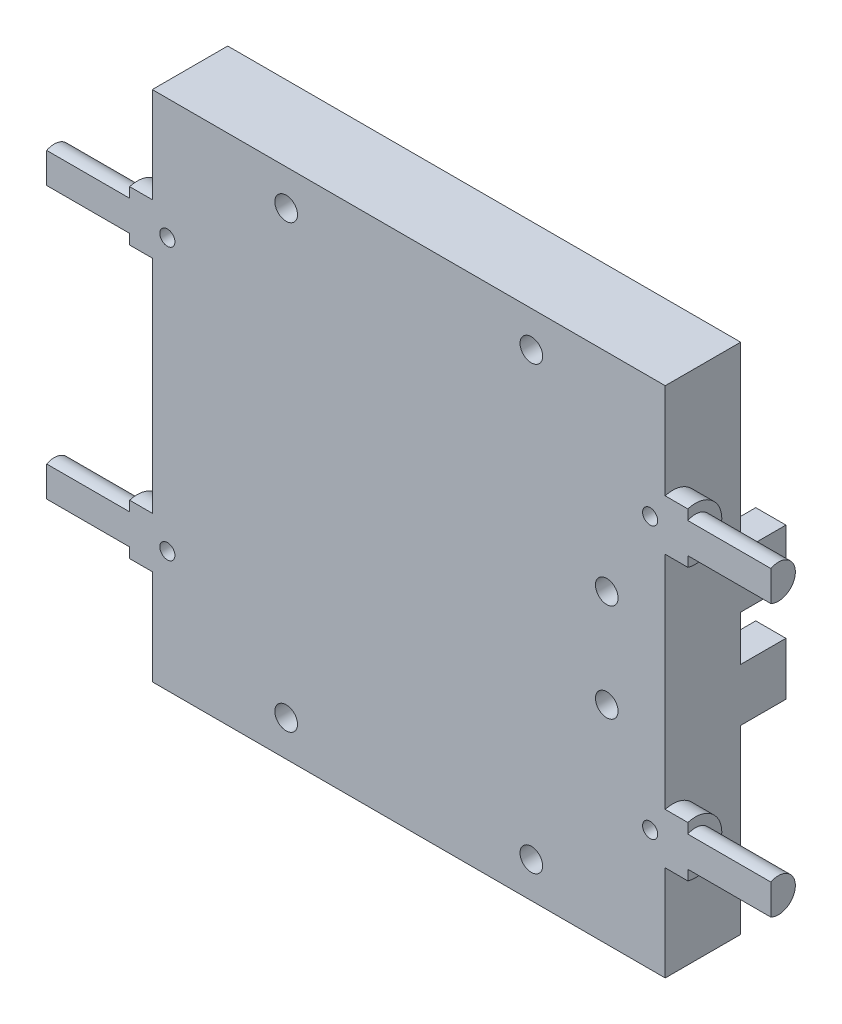
SolidWorks part; units mm, degrees
ref_plane "Front Plane" through (0, 0, 0) normal (0, 0, 1) x (1, 0, 0)
ref_plane "Top Plane" through (0, 0, 0) normal (0, 1, 0) x (1, 0, 0)
ref_plane "Right Plane" through (0, 0, 0) normal (1, 0, 0) x (0, 0, -1)
sketch "Sketch1" plane through (0, 0, 0) normal (0, 0, 1) x (1, 0, 0)
  line L1 (0, 0) -> (-68, 0)
  line L2 (0, 0) -> (0, -68)
  line L3 (0, -68) -> (-68, -68)
  line L4 (-68, 0) -> (-68, -68)
  dimension "D1" = 68
  dimension "D2" = 68
extrude "Boss-Extrude1" add sketch "Sketch1" along normal blind 10
sketch "Sketch2" plane through (-68, 0, 0) normal (-1, 0, 0) x (0, 0, 1)
  line L1 (10, 0) -> (0, 0) construction
  line L2 (10, -68) -> (0, -68) construction
  line L3 (10, 0) -> (10, -68) construction
  line L4 (10, 0) -> (10, -68)
  circle A0 centre (9, -52) radius 3.5
  circle A1 centre (9, -16) radius 3.5
  dimension "D1" = 7
  dimension "D2" = 7
  dimension "D3" = 1
  dimension "D4" = 0
  dimension "D5" = 16
  dimension "D6" = 16
extrude "Boss-Extrude2" add sketch "Sketch2" along normal blind 3 contours L4 A1 | L4 A0 region at (-68, -52, 8.0379) region at (-68, -16, 8.0379)
sketch "Sketch3" plane through (-71, 0, 0) normal (-1, 0, 0) x (0, 0, 1)
  line L0 (10, -55.3541) -> (10, -12.6459)
  circle A0 centre (9, -52) radius 2.25
  circle A1 centre (9, -16) radius 2.25
  dimension "D1" = 4.5
  dimension "D2" = 4.5
extrude "Boss-Extrude3" add sketch "Sketch3" along normal blind 11 contours L0 A0 | L0 A1 region at (-71, -52, 8.5562) region at (-71, -16, 8.5562)
sketch "Sketch4" plane through (0, 0, 0) normal (1, 0, 0) x (0, 0, -1)
  line L0 (-10, 0) -> (0, 0) construction
  line L1 (-10, -68) -> (0, -68) construction
  line L2 (-10, 0) -> (-10, -68)
  circle A0 centre (-9, -16) radius 3.5
  circle A1 centre (-9, -52) radius 3.5
  dimension "D1" = 16
  dimension "D2" = 16
  dimension "D3" = 7
  dimension "D4" = 7
  dimension "D5" = 1
  dimension "D6" = 0
extrude "Boss-Extrude4" add sketch "Sketch4" along normal blind 3 contours L2 A0 | L2 A1 region at (0, -16, 8.0379) region at (0, -52, 8.0379)
sketch "Sketch5" plane through (3, 0, 0) normal (1, 0, 0) x (0, 0, -1)
  line L0 (-10, -12.6459) -> (-10, -55.3541)
  circle A0 centre (-9, -16) radius 2.25
  circle A1 centre (-9, -52) radius 2.25
  dimension "D1" = 4.5
  dimension "D2" = 4.5
extrude "Boss-Extrude5" add sketch "Sketch5" along normal blind 11 contours L0 A0 | L0 A1 region at (3, -16, 8.5562) region at (3, -52, 8.5562)
sketch "Sketch6" plane through (0, 0, 0) normal (0, 0, -1) x (-1, 0, 0)
  line L0 (0, -34) -> (68, -34) construction
  line L1 (55.25, -12.75) -> (12.75, -12.75)
  line L2 (55.25, -12.75) -> (55.25, -55.25)
  line L3 (55.25, -55.25) -> (12.75, -55.25)
  line L4 (12.75, -12.75) -> (12.75, -55.25)
  line L5 (0, -68) -> (0, 0) construction
  line L6 (68, 0) -> (68, -68) construction
  line L7 (34, 0) -> (34, -68) construction
  line L8 (0, 0) -> (68, 0) construction
  line L9 (68, -68) -> (0, -68) construction
  point P16 (12.75, -34)
  point P17 (34, -55.25)
  dimension "D1" = 42.5
  dimension "D2" = 42.5
  dimension "D3" = 0
  dimension "D4" = 0
extrude "Cut-Extrude1" cut sketch "Sketch6" against normal blind 3
sketch "Sketch8" plane through (0, 0, 0) normal (0, 0, -1) x (-1, 0, 0)
  line L0 (55.25, -12.75) -> (12.75, -12.75) construction
  line L2 (12.75, -12.75) -> (12.75, -55.25) construction
  line L3 (34, 0) -> (34, -108.8236) construction
  line L4 (0, 0) -> (68, 0) construction
  line L5 (0, -34) -> (112.3527, -34) construction
  line L6 (0, -68) -> (0, 0) construction
  circle A0 centre (17.75, -4.75) radius 1.5
  circle A3 centre (50.25, -4.75) radius 1.5
  circle A4 centre (50.25, -63.25) radius 1.5
  circle A5 centre (17.75, -63.25) radius 1.5
  dimension "D1" = 8
  dimension "D3" = 3
  dimension "D5" = 5
extrude "Cut-Extrude2" cut sketch "Sketch8" against normal blind 15
sketch "Sketch9" plane through (0, 0, 0) normal (0, 0, -1) x (-1, 0, 0)
  line L1 (0, -24) -> (4, -24)
  line L2 (0, -24) -> (0, -31)
  line L3 (0, -31) -> (4, -31)
  line L4 (4, -24) -> (4, -31)
  line L5 (0, -68) -> (0, 0) construction
  line L6 (0, -34) -> (68, -34) construction
  line L7 (68, 0) -> (68, -68) construction
  line L8 (0, -37) -> (4, -37)
  line L9 (4, -44) -> (4, -37)
  line L10 (0, -44) -> (4, -44)
  line L11 (0, -44) -> (0, -37)
  point P6 (0, -34)
  dimension "D1" = 4
  dimension "D2" = 7
  dimension "D3" = 0
  dimension "D4" = 3
extrude "Boss-Extrude6" add sketch "Sketch9" along normal blind 6
sketch "Sketch10" plane through (0, 0, 0) normal (0, 0, -1) x (-1, 0, 0)
  line L0 (0, -34) -> (23.3312, -34) construction
  line L1 (0, -37) -> (0, -31) construction
  line L2 (12.75, -12.75) -> (12.75, -55.25) construction
  line L3 (4, -31) -> (4, -24) construction
  circle A0 centre (7.75, -27.5) radius 1.5
  circle A1 centre (7.75, -40.5) radius 1.5
  point P10 (4, -27.5)
  dimension "D1" = 3
  dimension "D2" = 5
  dimension "D3" = 0
extrude "Cut-Extrude3" cut sketch "Sketch10" against normal blind 10
sketch "Sketch11" plane through (0, 0, 10) normal (0, 0, 1) x (1, 0, 0)
  line L0 (-68, -34) -> (19.7059, -34) construction
  line L1 (-68, -19.3541) -> (-68, -48.6459) construction
  line L2 (-34, -68) -> (-34, 32.0149) construction
  line L3 (-68, -68) -> (0, -68) construction
  line L4 (-82, -54.0156) -> (-82, -49.9844) construction
  circle A0 centre (-66, -52) radius 1
  circle A1 centre (-66, -16) radius 1
  circle A2 centre (-2, -52) radius 1
  circle A3 centre (-2, -16) radius 1
  point P12 (-82, -52)
  dimension "D1" = 16
  dimension "D2" = 0
  dimension "D3" = 2
extrude "Cut-Extrude4" cut sketch "Sketch11" against normal blind 20
sketch "Sketch13" plane through (0, 0, 0) normal (0, 0, -1) x (-1, 0, 0)
  line L0 (68, 0) -> (68, -68) construction
  line L1 (59, -26) -> (66, -26)
  line L2 (59, -26) -> (59, -42)
  line L3 (59, -42) -> (66, -42)
  line L4 (66, -26) -> (66, -42)
  point P4 (66, -34)
  point P7 (68, -34)
  dimension "D1" = 7
  dimension "D2" = 0
  dimension "D3" = 16
  dimension "D4" = 2
extrude "Boss-Extrude7" add sketch "Sketch13" along normal blind 12
sketch "Sketch15" plane through (-66, 0, 0) normal (-1, 0, 0) x (0, 0, 1)
  line L0 (-12, -34) -> (24.0661, -34) construction
  line L1 (-12, -42) -> (-12, -26) construction
  line L2 (-12, -32) -> (-3, -32)
  line L3 (-3, -32) -> (-5, -30)
  line L4 (-5, -30) -> (-12, -30)
  line L5 (-12, -30) -> (-12, -32)
  line L6 (-12, -26) -> (0, -26) construction
  line L7 (-12, -38) -> (-12, -36)
  line L8 (-3, -36) -> (-5, -38)
  line L9 (-5, -38) -> (-12, -38)
  line L10 (-12, -36) -> (-3, -36)
  dimension "D1" = 2
  dimension "D2" = 4
  dimension "D3" = 45
  dimension "D4" = 7
extrude "Cut-Extrude5" cut sketch "Sketch15" against normal blind 10
sketch "Sketch16" plane through (-66, 0, 0) normal (-1, 0, 0) x (0, 0, 1)
  line L0 (0, -26) -> (-12, -26)
  line L1 (-12, -26) -> (0, -21)
  line L2 (0, -21) -> (0, -26)
  line L3 (-12, -34) -> (21.219, -34) construction
  line L4 (-12, -36) -> (-12, -32) construction
  line L5 (-12, -42) -> (0, -47)
  line L6 (0, -42) -> (-12, -42)
  line L7 (0, -47) -> (0, -42)
  dimension "D1" = 5
extrude "Boss-Extrude8" add sketch "Sketch16" against normal up to vertex (7 mm away) up to point (-59, -26, -12)
